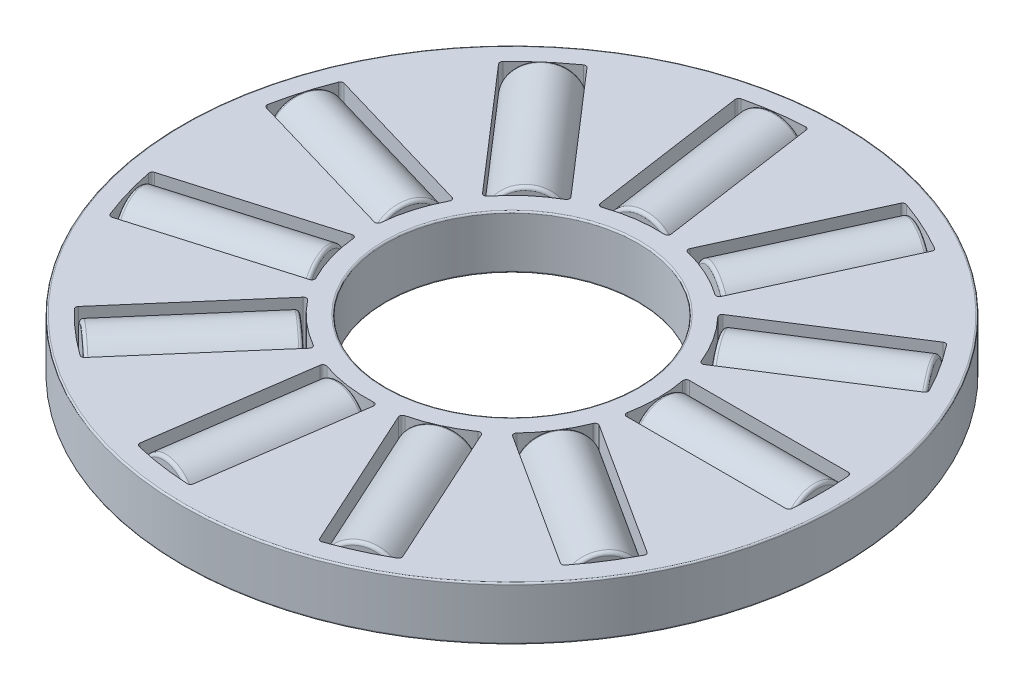
SolidWorks part; units mm, degrees
ref_plane "Front Plane" through (0, 0, 0) normal (0, 0, 1) x (1, 0, 0)
ref_plane "Top Plane" through (0, 0, 0) normal (0, 1, 0) x (1, 0, 0)
ref_plane "Right Plane" through (0, 0, 0) normal (1, 0, 0) x (0, 0, -1)
sketch "Sketch1" plane through (0, 0, 0) normal (1, 0, 0) x (0, 0, -1)
  line L0 (-10.5, 0) -> (10.5, 0) construction
  line L1 (-4.0125, 0) -> (4.0125, 0) construction
  line L2 (10.5, -1) -> (10.5, 1) construction
  line L3 (4.0125, -0.85) -> (4.0125, 0.85) construction
  line L23 (10, 0.85) -> (10.5, 0.85) construction
  line L32 (0, 1) -> (0, -1) construction
  line L33 (-4.5, 1) -> (4.5, 1) construction
  line L34 (-10, 0.85) -> (10, 0.85) construction
  point P4 (0, 0)
  point P8 (0, 0)
  point P11 (10.5, 0)
  point P14 (4.0125, 0)
  point P45 (0, 1)
  point P48 (0, 0)
  point P49 (0, 1)
  point P55 (0, 0.85)
  dimension "OD" = 21
  dimension "ID" = 8.025
  dimension "Thickness" = 2
  dimension "Approx. Raceway Thickness" = 1.7
  dimension "Inner Raceway" = 9
  dimension "Outer Raceway" = 20
sketch "Sketch2" plane through (0, 0, 0) normal (0, 1, 0) x (1, 0, 0)
  line L0 (4.5, 0) -> (10, 0) construction
  line L1 (9.8625, 0) -> (4.6375, 0)
  line L2 (9.8118, -0.9983) -> (4.5288, -0.9983)
  line L3 (9.8118, 0.9983) -> (4.5288, 0.9983)
  circle A0 centre (0, 0) radius 4.0125
  circle A1 centre (0, 0) radius 4.5
  circle A2 centre (0, 0) radius 10
  circle A3 centre (0, 0) radius 10.5
  arc A4 (4.5288, -0.9983) -> (4.5288, 0.9983) centre (0, 0) ccw
  arc A5 (9.8118, -0.9983) -> (9.8118, 0.9983) centre (0, 0) ccw
  arc A6 (9.8118, 0.9983) -> (9.4677, 2.7625) centre (0, 0) ccw
  point P15 (7.25, 0)
  dimension "Approx. Roller Seat Length" = 5.225
  dimension "Roller Width" = 2
  dimension "Approx. Roller Gap" = 1.8
sketch "Sketch3" plane through (0, 0, 0) normal (1, 0, 0) x (0, 0, -1)
  line L24 (10.5, -1) -> (10.5, 1) construction
  line L25 (4.0125, 0.85) -> (10.5, 0.85)
  line L26 (4.0125, 0.85) -> (4.0125, -0.85)
  line L27 (4.0125, -0.85) -> (10.5, -0.85)
  line L28 (10.5, 0.85) -> (10.5, -0.85)
revolve "Revolve1" add sketch "Sketch3" angle 360 about L32
fillet "Fillet1" radius 0.05 4 edges at (0, -0.85, 4.0125) (0, -0.85, 10.5) (0, 0.85, 10.5) (0, 0.85, 4.0125)
sketch "Sketch4" plane through (0, 0, 0) normal (0, 1, 0) x (1, 0, 0)
  line L0 (4.5288, 0.9983) -> (9.8118, 0.9983)
  line L1 (4.5288, -0.9983) -> (9.8118, -0.9983)
  arc A0 (4.5288, -0.9983) -> (4.5288, 0.9983) centre (0, 0) ccw construction
  arc A1 (4.5288, -0.9983) -> (4.5288, 0.9983) centre (0, 0) ccw
  arc A2 (9.8118, -0.9983) -> (9.8118, 0.9983) centre (0, 0) ccw construction
  arc A3 (9.8118, -0.9983) -> (9.8118, 0.9983) centre (0, 0) ccw
extrude "Cut-Extrude1" cut sketch "Sketch4" against normal through all both and the other way through all
fillet "Fillet5" radius 0.1 4 edges at (9.8118, 0, -0.9983) (9.8118, 0, 0.9983) (4.5288, 0, -0.9983) (4.5288, 0, 0.9983)
pattern_circular "CirPattern1" count 11 over 360 about axis through (0, 1, 0) along (0, -1, 0) of "Cut-Extrude1", "Fillet5"
sketch "Sketch5" plane through (0, 0, 0) normal (0, 1, 0) x (1, 0, 0)
  line L0 (4.7681, 0) -> (4.7681, 0.9983)
  line L1 (9.8118, 0.9983) -> (4.5288, 0.9983) construction
  line L2 (4.7681, 0.9983) -> (9.7319, 0.9983)
  line L3 (9.7319, 0.9983) -> (9.7319, 0)
  line L4 (9.7319, 0) -> (4.7681, 0)
  line L6 (9.8625, 0) -> (4.6375, 0) construction
  dimension "D1" = 4.9637
revolve "Revolve2" add sketch "Sketch5" angle 360 about L1
fillet "Fillet6" radius 0.1 2 edges at (4.7681, 0, -0.9983) (9.7319, 0, -0.9983)
pattern_circular "CirPattern2" count 11 over 360 about axis through (0, 1, 0) along (0, -1, 0) of bodies 107
ref_axis "Center Axis 1" through (0, -1.0981, 0) along (0, 1, 0)
ref_plane "Contact Plane 1" through (0, 1, 0) normal (0, 1, 0) x (1, 0, 0)
ref_plane "Contact Plane 2" through (0, -1, 0) normal (0, 1, 0) x (1, 0, 0)
equation "\"Approx. Raceway Thickness@Sketch1\" = \"Thickness@Sketch1\" * .85"
equation "\"D1@Fillet1\"=\"Thickness@Sketch1\" * .025"
equation "\"Approx. Roller Seat Length@Sketch2\" = \"Raceway Diff\" / 2 * .95"
equation "\"Approx. Roller Gap@Sketch2\" = \"Roller Width@Sketch2\" * .9"
equation "\"Raceway Diff\"= ( \"Outer Raceway@Sketch1\" - \"Inner Raceway@Sketch1\" )"
equation "\"Circumference\"= ( \"Inner Raceway@Sketch1\" + ( \"Raceway Diff\" / 2 ) ) * 3.14"
equation "\"Instances\"= int ( \"Circumference\" /  ( \"Roller Width@Sketch2\" + \"Approx. Roller Gap@Sketch2\" )  ) "
equation "\"D1@CirPattern1\"=\"Instances\""
equation "\"Roller Width@Sketch2\" = \"Thickness@Sketch1\""
equation "\"D1@Fillet5\" = \"Roller Width@Sketch2\" / 20"
equation "\"D1@Fillet6\" = \"Roller Width@Sketch2\" / 20"
equation "\"D1@CirPattern2\" = \"D1@CirPattern1\""
equation "\"D1@Sketch5\" = \"Approx. Roller Seat Length@Sketch2\" * .95"
